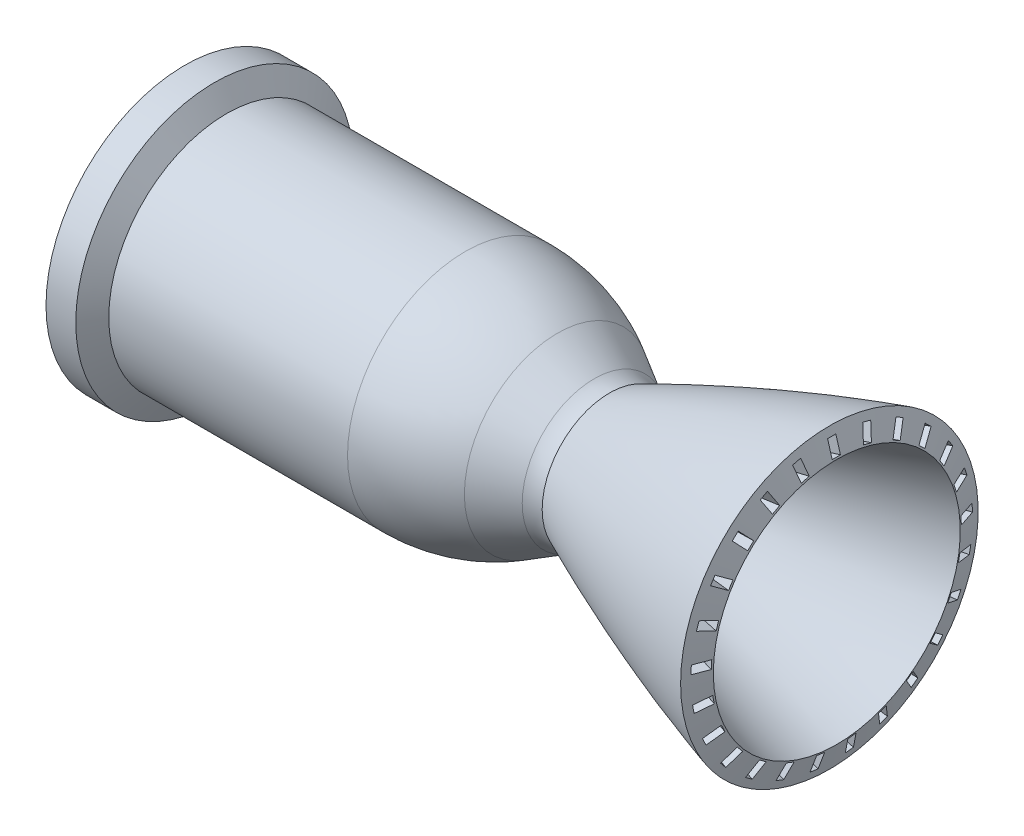
SolidWorks part; units mm, degrees
ref_plane "Front Plane" through (0, 0, 0) normal (0, 0, 1) x (1, 0, 0)
ref_plane "Top Plane" through (0, 0, 0) normal (0, 1, 0) x (1, 0, 0)
ref_plane "Right Plane" through (0, 0, 0) normal (1, 0, 0) x (0, 0, -1)
sketch "Sketch2" plane through (0, 0, 0) normal (0, 0, 1) x (1, 0, 0)
  line L0 (0, 55.5012) -> (144.9347, 55.5012)
  line L1 (192.877, 42.655) -> (215.1271, 29.8089)
  line L2 (0, 0) -> (370.4363, 0) construction
  line L3 (0, 0) -> (0, 55.5012) construction
  line L4 (0, 0) -> (290.4856, 0) construction
  line L5 (290.4856, 0) -> (290.4856, 47.6713) construction
  arc A0 (192.877, 42.655) -> (144.9347, 55.5012) centre (144.9346, -40.3836) ccw
  arc A1 (215.1271, 29.8089) -> (233.7428, 24.8208) centre (233.7428, 62.0521) ccw
  arc A2 (233.7428, 24.8208) -> (237.5976, 25.6398) centre (233.7428, 34.3024) ccw
  spline S0 degree 2 poles (237.5976, 25.6398) (305.7949, 55.9872) (370.4363, 74.9571) knots 0 0 0 1 1 1
  dimension "D4" = 95.8847
  dimension "D5" = 37.2313
  dimension "D6" = 9.4816
  dimension "D1" = 111.0023
  dimension "D2" = 49.6417
  dimension "D3" = 149.9142
  dimension "D7" = 144.9347
  dimension "D8" = 233.7428
  dimension "D9" = 370.4363
  dimension "D10" = 192.877
  dimension "D11" = 215.1271
  dimension "D12" = 237.5976
  dimension "D13" = 30
  dimension "D14" = 290.4856
sketch "Sketch12" plane through (0, 0, 0) normal (0, 0, 1) x (1, 0, 0)
  line L0 (192.877, 42.655) -> (215.1271, 29.8089) construction
  line L1 (0, 55.5012) -> (144.9347, 55.5012) construction
  line L2 (192.877, 42.655) -> (215.1271, 29.8089)
  line L3 (0, 55.5012) -> (144.9347, 55.5012)
  line L4 (0, 71.5012) -> (144.9347, 71.5012)
  line L5 (200.877, 56.5114) -> (223.1272, 43.6653)
  line L6 (0, 55.5012) -> (0, 71.5012)
  line L7 (370.4363, 74.9571) -> (365.9309, 90.3097)
  line L8 (0, 0) -> (96.0377, 0) construction
  arc A0 (233.7428, 24.8208) -> (237.5976, 25.6398) centre (233.7428, 34.3024) ccw construction
  arc A1 (215.1271, 29.8089) -> (233.7428, 24.8208) centre (233.7428, 62.0521) ccw construction
  arc A2 (192.877, 42.655) -> (144.9347, 55.5012) centre (144.9346, -40.3836) ccw construction
  arc A3 (233.7428, 24.8208) -> (237.5976, 25.6398) centre (233.7428, 34.3024) ccw
  arc A4 (215.1271, 29.8089) -> (233.7428, 24.8208) centre (233.7428, 62.0521) ccw
  arc A5 (192.877, 42.655) -> (144.9347, 55.5012) centre (144.9346, -40.3836) ccw
  arc A6 (200.877, 56.5114) -> (144.9347, 71.5012) centre (144.9346, -40.3836) ccw
  arc A7 (223.1272, 43.6653) -> (232.4488, 40.8603) centre (233.7428, 62.0521) ccw
  arc A8 (232.4488, 40.8603) -> (232.4488, 40.8603) centre (232.4488, 40.8603) ccw
  parabola Q0 (237.5976, 25.6398) -> (370.4363, 74.9571) focus (662.3735, -169.4319) apex (740.9638, 82.0231) construction
  parabola Q1 (237.5976, 25.6398) -> (370.4363, 74.9571) focus (662.3735, -169.4319) apex (740.9638, 82.0231)
  spline S0 degree 1 poles (232.4488, 40.8603) (365.9309, 90.3097) knots 0 0 1 1 construction
  spline S1 degree 3 poles (232.4488, 40.8603) (235.2883, 42.1199) (240.9897, 44.6236) (252.3263, 49.5002) (266.4446, 55.3824) (283.2803, 62.0891) (300.016, 68.4464) (316.65, 74.4531) (333.1842, 80.1095) (346.8752, 84.5296) (357.7853, 87.8924) (363.2095, 89.511) (365.9309, 90.3097) knots 0.492876 0.492876 0.492876 0.492876 0.492983 0.49309 0.493303 0.493517 0.493731 0.493944 0.494158 0.494372 0.494478 0.494585 0.494585 0.494585 0.494585
  dimension "D1" = 16
revolve "Revolve1" add sketch "Sketch12" angle 360 about L8
sketch "Sketch14" plane through (0, 0, 0) normal (0, 0, 1) x (1, 0, 0)
  line L0 (192.877, 42.655) -> (215.1271, 29.8089) construction
  line L1 (0, 55.5012) -> (144.9347, 55.5012) construction
  line L2 (192.877, 42.655) -> (215.1271, 29.8089) construction
  line L3 (0, 55.5012) -> (144.9347, 55.5012) construction
  line L4 (0, 56.5012) -> (144.9347, 56.5012)
  line L5 (193.377, 43.521) -> (215.6272, 30.6749)
  line L6 (0, 66.5012) -> (144.9347, 66.5012)
  line L7 (198.377, 52.1813) -> (220.6272, 39.3352)
  line L8 (0, 66.5012) -> (0, 56.5012)
  line L9 (370.1547, 75.9166) -> (367.3388, 85.512)
  arc A0 (233.7428, 24.8208) -> (237.5976, 25.6398) centre (233.7428, 34.3024) ccw construction
  arc A1 (215.1271, 29.8089) -> (233.7428, 24.8208) centre (233.7428, 62.0521) ccw construction
  arc A2 (192.877, 42.655) -> (144.9347, 55.5012) centre (144.9346, -40.3836) ccw construction
  arc A3 (233.7428, 24.8208) -> (237.5976, 25.6398) centre (233.7428, 34.3024) ccw construction
  arc A4 (215.1271, 29.8089) -> (233.7428, 24.8208) centre (233.7428, 62.0521) ccw construction
  arc A5 (192.877, 42.655) -> (144.9347, 55.5012) centre (144.9346, -40.3836) ccw construction
  arc A6 (193.377, 43.521) -> (144.9347, 56.5012) centre (144.9346, -40.3836) ccw
  arc A7 (215.6272, 30.6749) -> (233.7428, 25.8208) centre (233.7428, 62.0521) ccw
  arc A8 (233.7428, 25.8208) -> (237.191, 26.5534) centre (233.7428, 34.3024) ccw
  arc A9 (198.377, 52.1813) -> (144.9347, 66.5012) centre (144.9346, -40.3836) ccw
  arc A10 (220.6272, 39.3352) -> (233.4246, 35.8228) centre (233.7428, 62.0521) ccw
  arc A11 (233.4246, 35.8228) -> (233.4246, 35.8228) centre (233.4246, 35.8228) ccw
  parabola Q0 (237.5976, 25.6398) -> (370.4363, 74.9571) focus (662.3735, -169.4319) apex (740.9638, 82.0231) construction
  parabola Q1 (237.5976, 25.6398) -> (370.4363, 74.9571) focus (662.3735, -169.4319) apex (740.9638, 82.0231) construction
  spline S0 degree 1 poles (237.191, 26.5534) (370.1547, 75.9166) knots 0 0 1 1 construction
  spline S1 degree 3 poles (237.191, 26.5534) (240.0255, 27.8148) (245.7175, 30.3221) (257.0309, 35.2033) (271.115, 41.0877) (287.9003, 47.7912) (304.5764, 54.1396) (321.1412, 60.1321) (337.5967, 65.7694) (351.2137, 70.1696) (362.0602, 73.5143) (367.4501, 75.1229) (370.1547, 75.9166) knots 0.492859 0.492859 0.492859 0.492859 0.492967 0.493075 0.493291 0.493506 0.493722 0.493938 0.494154 0.494369 0.494477 0.494585 0.494585 0.494585 0.494585
  spline S2 degree 1 poles (233.4246, 35.8228) (367.3388, 85.512) knots 0 0 1 1 construction
  spline S3 degree 3 poles (233.4246, 35.8228) (236.2756, 37.0905) (242.0003, 39.6106) (253.3814, 44.5178) (267.5532, 50.4352) (284.4491, 57.179) (301.241, 63.5685) (317.9271, 69.6025) (334.5093, 75.2814) (348.2367, 79.7164) (359.1742, 83.0889) (364.6109, 84.7114) (367.3388, 85.512) knots 0.492863 0.492863 0.492863 0.492863 0.49297 0.493078 0.493293 0.493509 0.493724 0.493939 0.494155 0.49437 0.494478 0.494585 0.494585 0.494585 0.494585
  dimension "D2" = 11
extrude "Cut-Extrude1" cut sketch "Sketch14" against normal mid plane 5
pattern_circular "CirPattern1" count 25 over 360 about axis through (0, 0, 0) along (1, 0, 0) of "Cut-Extrude1"
sketch "Sketch15" plane through (0, 0, 0) normal (0, 0, 1) x (1, 0, 0)
  line L0 (0, 71.5012) -> (0, -71.5012) construction
  line L1 (0, 71.5012) -> (0, -71.5012) construction
  line L3 (144.9347, 66.5012) -> (0, 66.5012) construction
  line L4 (144.9347, 66.5012) -> (0, 66.5012) construction
  line L5 (0, 71.5012) -> (-7.3323, 84.2012)
  line L6 (-7.3323, 84.2012) -> (-25.4, 84.2012)
  line L7 (-25.4, 84.2012) -> (-25.4, 66.5012)
  line L8 (-25.4, 66.5012) -> (0, 66.5012)
  line L9 (0, 71.5012) -> (144.9347, 71.5012) construction
  line L10 (0, 71.5012) -> (144.9347, 71.5012) construction
  line L11 (0, 0) -> (77.7416, 0) construction
  line L12 (0, 71.5012) -> (0, 66.5012)
  dimension "D1" = 120
  dimension "D2" = 25.4
  dimension "D3" = 12.7
revolve "Revolve2" add sketch "Sketch15" angle 360 about L11
equation "\"Chamber Inner Wall Thickness\"= 1mm"
equation "\"Chamber Outer Wall Thickness\"= 5mm"
equation "\"Cooling Channel Height\"= 10mm"
equation "\"Cooling Channel Base\"= 5mm"
equation "\"D1@Sketch12\"=\"Chamber Inner Wall Thickness\"+\"Cooling Channel Height\"+\"Chamber Outer Wall Thickness\""
equation "\"D1@Sketch14\"=\"Chamber Inner Wall Thickness\""
equation "\"D2@Sketch14\"=\"Chamber Inner Wall Thickness\"+\"Cooling Channel Height\""
equation "\"D1@Cut-Extrude1\"=\"Cooling Channel Base\""
equation "\"Number of Cooling Channels\"= 25"
equation "\"D1@CirPattern1\"=\"Number of Cooling Channels\""
